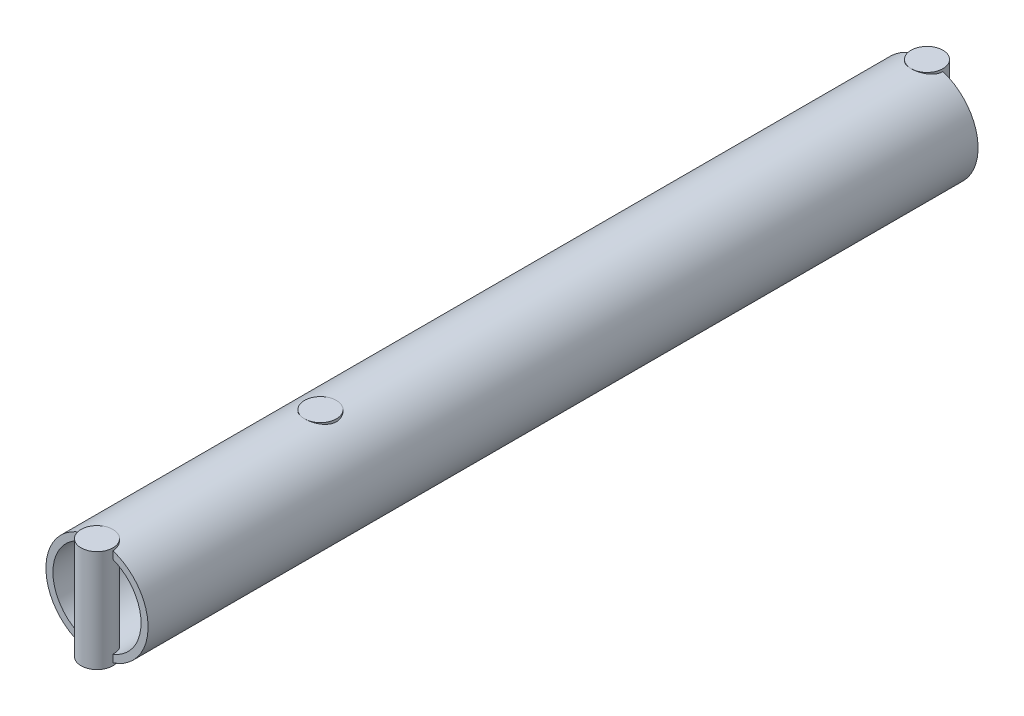
SolidWorks part; units mm, degrees
ref_plane "Front Plane" through (0, 0, 0) normal (0, 0, 1) x (1, 0, 0)
ref_plane "Top Plane" through (0, 0, 0) normal (0, 1, 0) x (1, 0, 0)
ref_plane "Right Plane" through (0, 0, 0) normal (1, 0, 0) x (0, 0, -1)
sketch "Sketch1" plane through (0, 0, 0) normal (0, 0, 1) x (1, 0, 0)
  circle A0 centre (0, 0) radius 8
  circle A1 centre (0, 0) radius 6.9
  dimension "D1" = 16
  dimension "D2" = 13.8
extrude "Boss-Extrude1" add sketch "Sketch1" along normal blind 130
sketch "Sketch2" plane through (0, 0, 0) normal (0, 1, 0) x (1, 0, 0)
  line L0 (-8, -130) -> (8, -130) construction
  line L1 (0, -95) -> (0, -130) construction
  circle A0 centre (0, 0) radius 2.5
  circle A1 centre (0, -130) radius 2.5
  circle A2 centre (0, -95) radius 2.5
  dimension "D1" = 5
  dimension "D2" = 35
extrude "Boss-Extrude2" add sketch "Sketch2" along normal blind 8 and the other way blind 8
